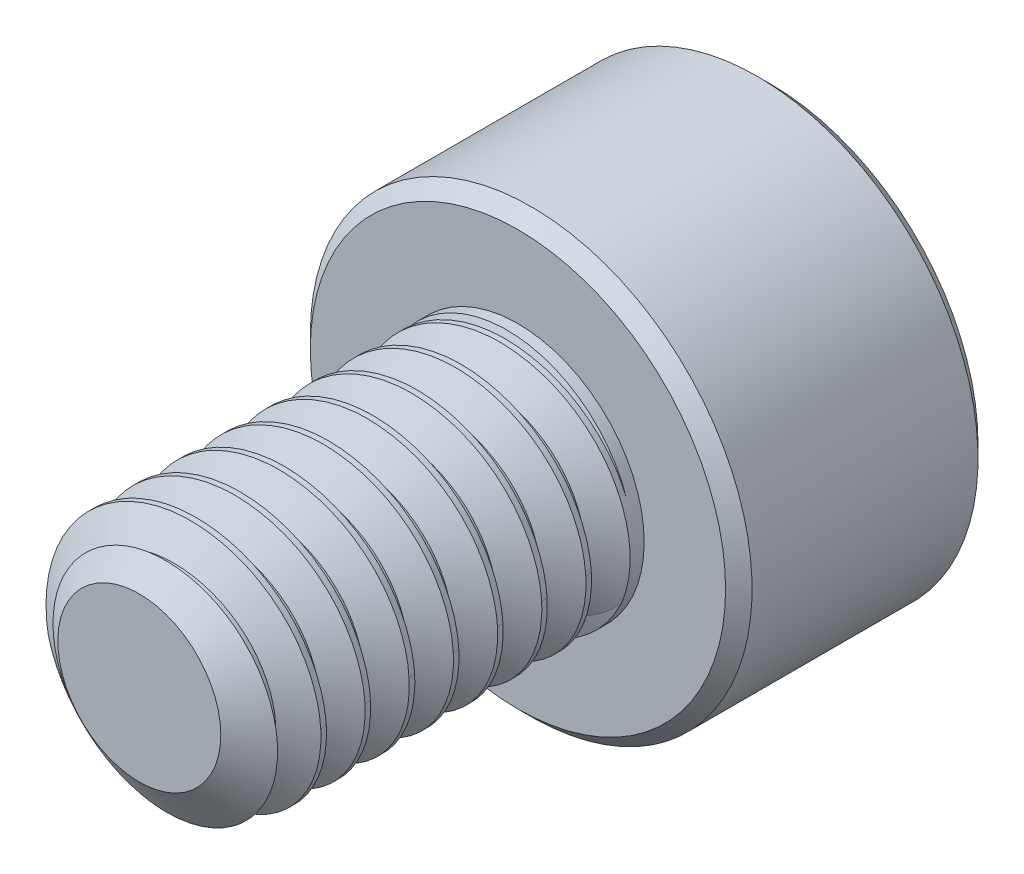
SolidWorks part; units mm, degrees
ref_plane "Front Plane" through (0, 0, 0) normal (0, 0, 1) x (1, 0, 0)
ref_plane "Top Plane" through (0, 0, 0) normal (0, 1, 0) x (1, 0, 0)
ref_plane "Right Plane" through (0, 0, 0) normal (1, 0, 0) x (0, 0, -1)
sketch "Sketch1" plane through (0, 0, 0) normal (0, 0, 1) x (1, 0, 0)
  circle A0 centre (0, 0) radius 2
  dimension "OD" = 4
extrude "Extrude1" add sketch "Sketch1" against normal blind 6
sketch "Sketch2" plane through (0, 0, 0) normal (0, 0, 1) x (1, 0, 0)
  circle A0 centre (0, 0) radius 2 construction
  circle A1 centre (0, 0) radius 2
curve "Helix/Spiral1" pitch 0.7 height 6.7 radius 2 centre (0, 0, 0) axis (0, 0, -1) start towards (0, 1, 0) parameters "pitch"=0.7
sketch "Sketch3" plane through (0, 0, 0) normal (1, 0, 0) x (0, 0, -1)
  line L0 (-0.6125, 2) -> (-0.35, 1.5453)
  line L1 (-0.35, 1.5453) -> (-0.2625, 1.5453)
  line L2 (-0.2625, 1.5453) -> (0, 2)
  line L3 (-0.6125, 2) -> (0, 2)
  line L4 (-0.3063, 2) -> (-0.3063, 1.5453) construction
  line L5 (-0.4813, 1.7727) -> (-0.1313, 1.7727) construction
  line L6 (0, 2) -> (0, -2) construction
  line L7 (0, -2) -> (6, -2) construction
  point P11 (3.15, -2)
  dimension "D1" = 0.0875
  dimension "D2" = 0.35
  dimension "D3" = 60
  dimension "D4" = 3.15
sweep "Cut-Sweep1" cut profiles "Sketch3" path "Helix/Spiral1" align with end faces yes
sketch "Sketch4" plane through (0, 0, 0) normal (1, 0, 0) x (0, 0, -1)
  line L0 (0.4962, 2) -> (0, 1.2913)
  line L1 (0, 1.2913) -> (0, 2)
  line L2 (0.4962, 2) -> (0, 2)
  line L3 (-0.6125, 2) -> (0, 2) construction
  line L4 (0, 0) -> (7.0209, 0) construction
  dimension "D1" = 55
  dimension "D2" = 0.254
revolve "Cut-Revolve1" cut sketch "Sketch4" angle 360 about L4
sketch "Sketch5" plane through (0, 0, 0) normal (1, 0, 0) x (0, 0, -1)
  line L0 (6, -1.8828) -> (6, 1.3901) construction
  line L1 (6, 2) -> (0.1203, 2)
  line L2 (6, 2) -> (6, 0)
  line L3 (6, 0) -> (0.0001, 0)
  line L4 (0.0001, 1.6698) -> (0.0001, 0)
  line L5 (0.1203, 2) -> (0.0001, 1.6698)
  line L6 (0, 0) -> (9.9695, 0) construction
  point P3 (0.0001, 2)
  point P10 (0.0001, 2)
  dimension "D1" = 0.3302
  dimension "Thread min" = 0.0001
  dimension "D3" = 20
revolve "partially thread" [suppressed] add sketch "Sketch5" angle 360 about L6
sketch "Sketch6" plane through (0, 0, -6) normal (0, 0, -1) x (-1, 0, 0)
  circle A0 centre (0, 0) radius 3.5
  dimension "head dia" = 7
extrude "Extrude2" add sketch "Sketch6" along normal blind 4
sketch "Sketch7" plane through (0, 0, -10) normal (0, 0, -1) x (-1, 0, 0)
  line L1 (0, 1.7321) -> (-1.5, 0.866)
  line L2 (-1.5, 0.866) -> (-1.5, -0.866)
  line L3 (-1.5, -0.866) -> (0, -1.7321)
  line L4 (0, -1.7321) -> (1.5, -0.866)
  line L5 (1.5, -0.866) -> (1.5, 0.866)
  line L6 (1.5, 0.866) -> (0, 1.7321)
  circle A0 centre (0, 0) radius 1.5 construction
  dimension "hex dia" = 3
extrude "Cut-Extrude1" cut sketch "Sketch7" against normal blind 2.25
sketch "Sketch8" plane through (0, 0, -10) normal (0, 0, -1) x (-1, 0, 0)
  circle A0 centre (0, 0) radius 1.7321
extrude "Cut-Extrude2" cut sketch "Sketch8" against normal through all draft 45
chamfer "Chamfer1" distance 0.21 angle 45 2 edges at (-3.5, 0, -10) (-3.5, 0, -6)
sketch "Sketch9" plane through (0, 0, 0) normal (1, 0, 0) x (0, 0, -1)
  line L0 (0, 2) -> (0, -2) construction
  line L1 (3.85, 2) -> (3.85, -2) construction
  dimension "D1" = 3.85
sketch "Sketch10" plane through (0, 0, 0) normal (1, 0, 0) x (0, 0, -1)
  line L0 (6, 2) -> (6, 0)
  line L1 (6, 2) -> (5.825, 2)
  line L2 (5.825, 2) -> (4.9966, 0)
  line L3 (6, 0) -> (4.9966, 0)
  line L4 (6, 3.29) -> (6, -3.29) construction
  dimension "D1" = 22.5
  dimension "D2" = 0.175
revolve "Revolve1" add sketch "Sketch10" angle 360 about L3
move or copy body "Body-Move/Copy1" [suppressed] bodies to move or copy 108
equation "\"D3@Helix/Spiral1\" = \"screw length@Extrude1\"+\"pitch@Helix/Spiral1\""
equation "\"D1@Sketch3\" = \"pitch@Helix/Spiral1\"*.125"
equation "\"D2@Sketch3\" = \"pitch@Helix/Spiral1\"*.5"
equation "\"D1@Cut-Extrude1\" = \"hex dia@Sketch7\"*.75"
equation "\"D1@Chamfer1\" = \"head dia@Sketch6\"*.03"
equation "\"D1@Sketch9\" = \"pitch@Helix/Spiral1\"*5.5"
equation "\"D2@Sketch10\" = \"pitch@Helix/Spiral1\"*.25"
equation "\"D4@Sketch3\" = \"pitch@Helix/Spiral1\"*4.50"
